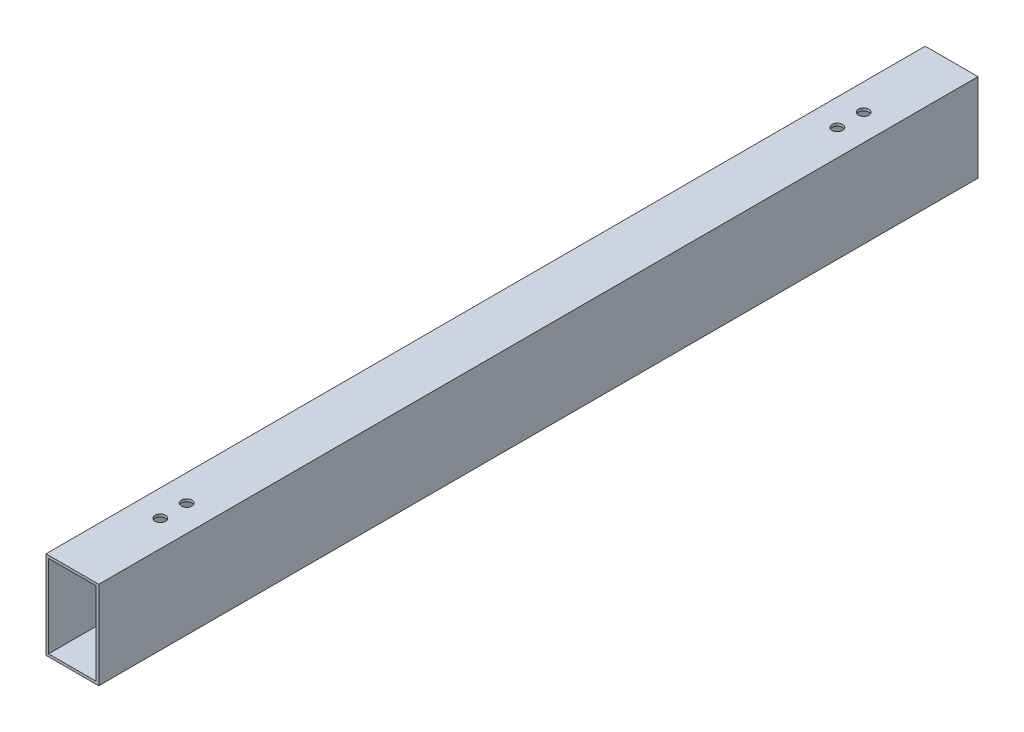
SolidWorks part; units mm, degrees
ref_plane "Płaszczyzna przednia" through (0, 0, 0) normal (0, 0, 1) x (1, 0, 0)
ref_plane "Płaszczyzna górna" through (0, 0, 0) normal (0, 1, 0) x (1, 0, 0)
ref_plane "Płaszczyzna prawa" through (0, 0, 0) normal (1, 0, 0) x (0, 0, -1)
sketch "Szkic1" plane through (0, 0, 0) normal (0, 0, 1) x (1, 0, 0)
  line L1 (0, 0) -> (30, 0)
  line L2 (0, 0) -> (0, 50)
  line L3 (0, 50) -> (30, 50)
  line L4 (30, 0) -> (30, 50)
  dimension "D1" = 50
  dimension "D2" = 30
sketch "Szkic2" plane through (0, 0, 0) normal (0, 0, 1) x (1, 0, 0)
  line L0 (30, 0) -> (30, 50) construction
  line L1 (1.5, 48.5) -> (28.5, 48.5)
  line L2 (1.5, 48.5) -> (1.5, 1.5)
  line L3 (1.5, 1.5) -> (28.5, 1.5)
  line L4 (28.5, 48.5) -> (28.5, 1.5)
  line L5 (0, 0) -> (0, 50) construction
  line L6 (0, 50) -> (30, 50) construction
  line L7 (0, 0) -> (30, 0) construction
  dimension "D1" = 1.5
  dimension "D2" = 1.5
  dimension "D3" = 1.5
  dimension "1,5" = 1.5
extrude "Dodanie-wyciągnięcie1" add sketch "Szkic1" along normal blind 500 contours L4 L3 L2 L1
extrude "Wytnij-wyciągnięcie7" cut sketch "Szkic2" along normal through all
sketch "Szkic5" plane through (0, 0, 0) normal (0, 1, 0) x (1, 0, 0)
  line L0 (0, -500) -> (0, 0) construction
  line L1 (0, -500) -> (30, -500) construction
  line L2 (0, 0) -> (30, 0) construction
  circle A0 centre (15, -450) radius 3
  circle A1 centre (15, -435) radius 3
  circle A2 centre (15, -50) radius 3
  circle A3 centre (15, -65) radius 3
  dimension "D1" = 6
  dimension "D2" = 15
  dimension "D3" = 50
  dimension "D4" = 6
  dimension "D5" = 15
  dimension "D6" = 15
  dimension "D7" = 6
  dimension "D8" = 15
  dimension "D9" = 50
  dimension "D10" = 6
  dimension "D11" = 15
  dimension "D12" = 15
extrude "Wytnij-wyciągnięcie13" cut sketch "Szkic5" along normal through all contours A3 | A2 | A1 | A0
